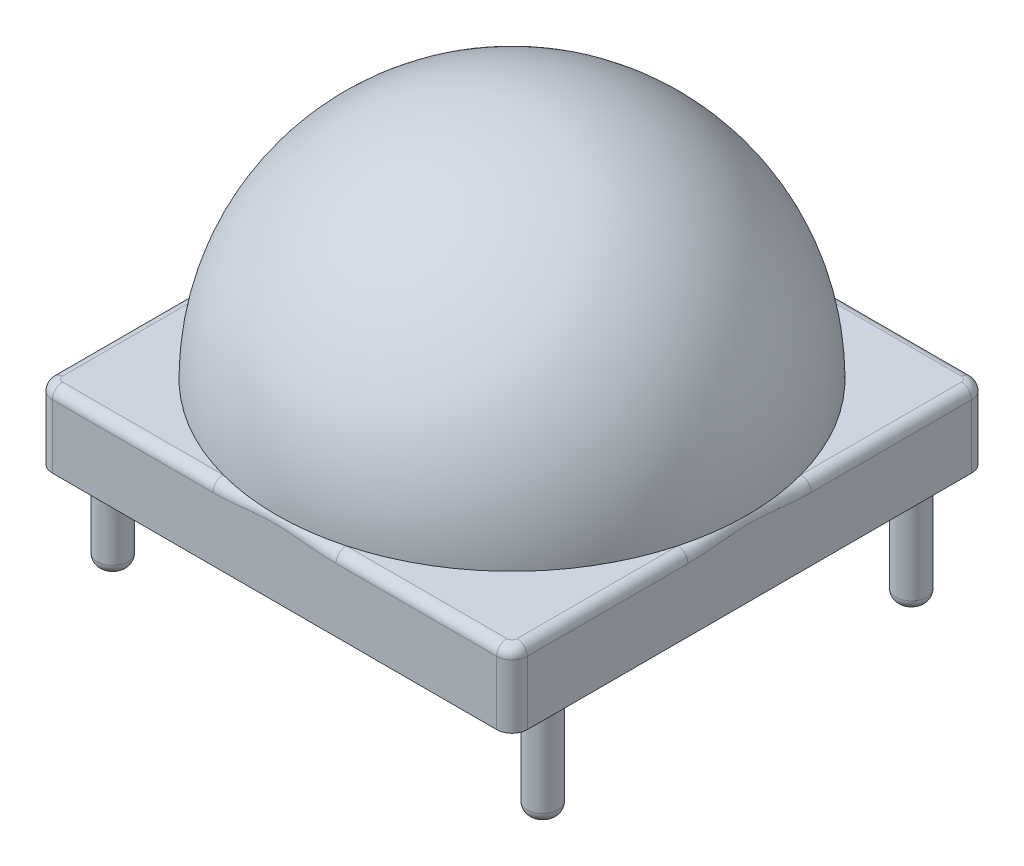
SolidWorks part; units mm, degrees
material "1060 Alloy"
ref_plane "Front" through (0, 0, 0) normal (0, 0, 1) x (1, 0, 0)
ref_plane "Top" through (0, 0, 0) normal (0, 1, 0) x (1, 0, 0)
ref_plane "Right" through (0, 0, 0) normal (1, 0, 0) x (0, 0, -1)
sketch "Sketch1" plane through (0, 0, 0) normal (0, 1, 0) x (1, 0, 0)
  line L1 (-11.6, -11.6) -> (11.6, -11.6)
  line L2 (-11.6, -11.6) -> (-11.6, 11.6)
  line L3 (-11.6, 11.6) -> (11.6, 11.6)
  line L4 (11.6, -11.6) -> (11.6, 11.6)
  line L5 (-11.6, -11.6) -> (11.6, 11.6) construction
  line L6 (-11.6, 11.6) -> (11.6, -11.6) construction
  point P0 (0, 0)
  dimension "D1" = 23.2
extrude "Boss-Extrude1" add sketch "Sketch1" along normal blind 2.6 and the other way blind 1
sketch "Sketch2" plane through (0, 0, 0) normal (1, 0, 0) x (0, 0, -1)
  line L0 (-11.6, 2.6) -> (11.6, 2.6) construction
  line L1 (0, -3.6976) -> (0, 18.9694) construction
  line L2 (0, 2.6) -> (11.5, 2.6)
  line L3 (0, 14.1) -> (0, 2.6)
  arc A0 (0, 14.1) -> (11.5, 2.6) centre (0, 2.6) cw
  dimension "D1" = 11.5
revolve "Revolve2" add sketch "Sketch2" angle 360 about L1
fillet "Fillet1" radius 0.75 4 edges at (-11.6, 0.8, -11.6) (-11.6, 0.8, 11.6) (11.6, 0.8, 11.6) (11.6, 0.8, -11.6)
shell "Shell2" thickness 2 removed face at (0, -1, 0)
sketch "Sketch3" plane through (0, -1, 0) normal (0, -1, 0) x (1, 0, 0)
  line L2 (0, 12.0407) -> (0, -12.7161) construction
  line L3 (-13.1845, 0) -> (16.3577, 0) construction
  circle A0 centre (-10.5, 9) radius 0.75
  circle A1 centre (10.5, 9) radius 0.75
  circle A2 centre (10.5, -9) radius 0.75
  circle A3 centre (-10.5, -9) radius 0.75
  dimension "D1" = 1.5
  dimension "D2" = 10.5
  dimension "D3" = 9
extrude "Boss-Extrude2" add sketch "Sketch3" along normal blind 5
ref_axis "Axis2" through (0, 50, 0) along (0, -1, 0)
sketch "Sketch7" plane through (0, 0, 0) normal (0, 1, 0) x (1, 0, 0)
  line L1 (3.2361, 1.0515) -> (0, 3.4026)
  line L2 (0, 3.4026) -> (-3.2361, 1.0515)
  line L3 (-3.2361, 1.0515) -> (-2, -2.7528)
  line L4 (-2, -2.7528) -> (2, -2.7528)
  line L5 (2, -2.7528) -> (3.2361, 1.0515)
  circle A0 centre (0, 0) radius 2.7528 construction
  dimension "D1" = 4
extrude "Cut-Extrude4" cut sketch "Sketch7" along normal blind 12
ref_plane "Plane3" through (5.9635, 9.734, 1.9377) normal (0.515, 0.8407, 0.1673) x (0.309, 0, -0.9511)
sketch "Sketch8" plane through (5.9635, 9.734, 1.9377) normal (0.515, 0.8407, 0.1673) x (0.309, 0, -0.9511)
  line L0 (-2, 4.1843) -> (2, 4.1843) construction
  line L1 (4, 0.7202) -> (2, 4.1843)
  line L2 (2, 4.1843) -> (-2, 4.1843)
  line L3 (-2, 4.1843) -> (-4, 0.7202)
  line L5 (-4, 0.7202) -> (-2, -2.7439)
  line L6 (-2, -2.7439) -> (2, -2.7439)
  line L7 (2, -2.7439) -> (4, 0.7202)
  circle A0 centre (0, 0.7202) radius 3.4641 construction
  dimension "D1" = 4
extrude "Cut-Extrude5" cut sketch "Sketch8" against normal blind 5
ref_axis "Axis3" through (0, -50, 0) along (0, 1, 0)
pattern_circular "CirPattern3" count 5 over 288 about axis through (0, -50, 0) along (0, 1, 0) of "Cut-Extrude5"
ref_plane "Plane4" through (-2.3297, 1.1775, -0.757) normal (-0.8572, 0.4332, -0.2785) x (0.309, 0, -0.9511)
ref_plane "Plane5" through (-9.4013, 4.7517, -3.0547) normal (-0.8572, 0.4332, -0.2785) x (0.309, 0, -0.9511)
sketch "Sketch9" plane through (-9.4013, 4.7517, -3.0547) normal (-0.8572, 0.4332, -0.2785) x (0.309, 0, -0.9511)
  line L0 (3.0779, -3.3017) -> (3.4235, -3.9183) construction
  line L1 (3.4482, 0.0192) -> (0, 2.0101)
  line L2 (0, 2.0101) -> (-3.4482, 0.0192)
  line L3 (-3.4482, 0.0192) -> (-3.4482, -3.9624)
  line L4 (-3.4482, -3.9624) -> (0, -5.9533)
  line L5 (0, -5.9533) -> (3.4482, -3.9624)
  line L6 (3.4482, -3.9624) -> (3.4482, 0.0192)
  line L7 (-3.0779, -3.3017) -> (-3.4235, -3.9183) construction
  circle A0 centre (0, -1.9716) radius 3.4482 construction
extrude "Cut-Extrude6" cut sketch "Sketch9" against normal blind 5
pattern_circular "CirPattern5" count 5 over 360 about axis through (0, -50, 0) along (0, 1, 0) of "Cut-Extrude6"
ref_plane "Plane6" through (-9.7323, 4.3707, 3.1622) normal (-0.8746, 0.3928, 0.2842) x (-0.309, 0, -0.9511)
sketch "Sketch10" plane through (-9.7323, 4.3707, 3.1622) normal (-0.8746, 0.3928, 0.2842) x (-0.309, 0, -0.9511)
  line L1 (1.9694, -4.2162) -> (-1.9694, -4.2162) construction
  line L2 (1.999, -4.2162) -> (3.2344, -0.4139)
  line L3 (3.2344, -0.4139) -> (0, 1.936)
  line L4 (0, 1.936) -> (-3.2344, -0.4139)
  line L5 (-3.2344, -0.4139) -> (-1.999, -4.2162)
  line L6 (-1.999, -4.2162) -> (1.999, -4.2162)
  circle A0 centre (0, -1.4648) radius 2.7514 construction
  point P9 (0, -4.2162)
  point P14 (0, -4.2162)
extrude "Cut-Extrude7" cut sketch "Sketch10" against normal blind 5
pattern_circular "CirPattern6" count 5 over 360 about axis through (0, -50, 0) along (0, 1, 0) of "Cut-Extrude7"
sketch "Sketch11" plane through (0, 0, 0) normal (1, 0, 0) x (0, 0, -1)
  line L0 (-3.28, 2.6) -> (3.3337, 2.6)
  line L1 (3.3337, 2.6) -> (3.3238, 2.9401)
  line L2 (3.3238, 2.9401) -> (-0.0359, 4.7514)
  line L3 (-0.0359, 4.7514) -> (-3.2843, 2.7475)
  line L4 (-3.2843, 2.7475) -> (-3.28, 2.6)
  line L5 (-10.85, 2.6) -> (10.85, 2.6) construction
  line L6 (0.1865, -2.879) -> (3.4349, -0.8751) [skipped]
  line L7 (-3.1731, -1.0677) -> (0.1865, -2.879) [skipped]
  arc A0 (2.9315, 2.6) -> (-2.7809, 2.6) centre (0.0753, 0.9362) ccw construction
extrude "Cut-Extrude8" cut sketch "Sketch11" along normal blind 10.5
pattern_circular "CirPattern7" count 10 over 360 about axis through (0, 50, 0) along (0, -1, 0) of "Cut-Extrude8"
fillet "Fillet2" radius 0.5 8 edges at (11.3803, 2.6, -11.3803) (11.6, 2.6, 0) (-11.6, 2.6, 0) (-11.3803, 2.6, -11.3803) (0, 2.6, -11.6) (11.3803, 2.6, 11.3803) (0, 2.6, 11.6) (-11.3803, 2.6, 11.3803)
fillet "Fillet3" radius 0.5 4 edges at (-10.5, -6, -8.25) (10.5, -6, -9.75) (10.5, -6, 9.75) (-10.5, -6, 8.25)
